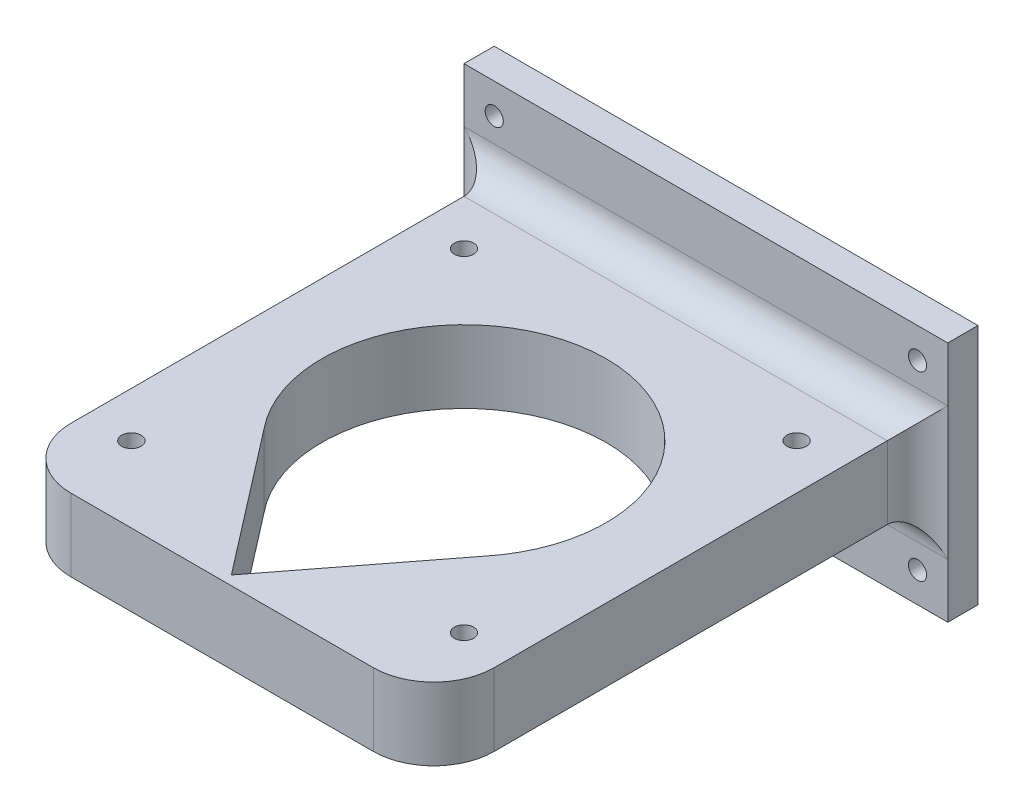
SolidWorks part; units mm, degrees
ref_plane "前视基准面" through (0, 0, 0) normal (0, 0, 1) x (1, 0, 0)
ref_plane "上视基准面" through (0, 0, 0) normal (0, 1, 0) x (1, 0, 0)
ref_plane "右视基准面" through (0, 0, 0) normal (1, 0, 0) x (0, 0, -1)
other "Configuration Table"
sketch "草图2" plane through (0, 0, 0) normal (0, 1, 0) x (1, 0, 0)
  line L1 (-35, -40) -> (35, -40)
  line L2 (-35, -40) -> (-35, 40)
  line L3 (-35, 40) -> (35, 40)
  line L4 (35, -40) -> (35, 40)
  line L5 (-35, -40) -> (35, 40) construction
  line L6 (-35, 40) -> (35, -40) construction
  line L7 (-27.5, -27.5) -> (27.5, -27.5)
  line L8 (-27.5, -27.5) -> (-27.5, 27.5)
  line L9 (-27.5, 27.5) -> (27.5, 27.5)
  line L10 (27.5, -27.5) -> (27.5, 27.5)
  line L11 (-27.5, -27.5) -> (27.5, 27.5) construction
  line L12 (-27.5, 27.5) -> (27.5, -27.5) construction
  circle A0 centre (0, 0) radius 23.5
  circle A1 centre (-27.5, 27.5) radius 1.6
  circle A2 centre (27.5, 27.5) radius 1.6
  circle A3 centre (27.5, -27.5) radius 1.6
  circle A4 centre (-27.5, -27.5) radius 1.6
  point P0 (0, 0)
  point P22 (0, 0)
  dimension "D2" = 47
  dimension "D6" = 3.2
  dimension "D1" = 70
  dimension "D3" = 80
  dimension "D4" = 55
  dimension "D5" = 55
  dimension "D7" = 4
extrude "凸台-拉伸4" add sketch "草图2" along normal blind 12 contours L1 L4 L3 L2 A4 L8 A1 L9 A2 L10 A3 L7 | A4 L7 A3 L10 A2 L9 A1 L8 A0 region at (-33.937, 0, 0) region at (-25.8186, 0, 25.8186)
sketch "草图6" plane through (0, 0, -40) normal (0, 0, -1) x (-1, 0, 0)
  line L0 (-1035, 6) -> (48965, 6) construction
  line L1 (-35, 12) -> (-35, 0) construction
  line L3 (-40, -14) -> (40, -14)
  line L4 (-40, -14) -> (-40, 26)
  line L5 (-40, 26) -> (40, 26)
  line L6 (40, -14) -> (40, 26)
  line L7 (-40, -14) -> (40, 26) construction
  line L8 (-40, 26) -> (40, -14) construction
  point P1 (0, 6)
  point P5 (-35, 6)
  dimension "D1" = 80
  dimension "D2" = 40
extrude "凸台-拉伸6" add sketch "草图6" along normal blind 5
fillet "圆角3" radius 5 1 edges at (0, 12, -40) type face fillet first side face at (-27.5, 12, -25.9) second side face at (0, 6, -40)
fillet "圆角4" radius 5 1 edges at (0, 0, -40) type face fillet first side face at (-27.5, 0, -25.9) second side face at (0, 6, -40)
fillet "圆角5" radius 5 1 edges at (35, 6, -40) type face fillet first side face at (35, 6, -12.0118) second side face at (0, 6, -40)
fillet "圆角6" radius 5 1 edges at (-35, 6, -40) type face fillet first side face at (1.25, 6, -40) second side face at (-35, 6, -12.0118)
sketch "草图7" plane through (0, 0, -40) normal (0, 0, 1) x (1, 0, 0)
  line L0 (-1040, 6) -> (48960, 6) construction
  line L1 (-40, -14) -> (-35, -14)
  line L2 (-40, -14) -> (-40, -9)
  line L3 (-40, -9) -> (-35, -9)
  line L4 (-35, -14) -> (-35, -9)
  line L5 (-40, -5) -> (-40, 17) construction
  line L6 (0, -974) -> (0, 49026) construction
  line L7 (-40, 26) -> (40, 26) construction
  circle A0 centre (-35, -9) radius 1.5
  circle A1 centre (-35, 21) radius 1.5
  circle A2 centre (35, -9) radius 1.5
  circle A3 centre (35, 21) radius 1.5
  point P11 (-40, 6)
  point P16 (0, 26)
  dimension "D3" = 3
  dimension "D1" = 5
  dimension "D2" = 5
extrude "切除-拉伸4" cut sketch "草图7" against normal blind 5 contours A1 | A3 | A2 | A0
sketch "草图8" plane through (0, 12, 0) normal (0, 1, 0) x (1, 0, 0)
  line L0 (0, 0) -> (0, -38.4612)
  line L1 (0, -38.4612) -> (-18.2335, -14.8253)
  line L2 (0, -38.4612) -> (18.2335, -14.8253)
  circle A0 centre (0, 0) radius 23.5 construction
  point P7 (18.2335, -14.8253)
  circle M11 centre (0, 0) radius 23.5
extrude "切除-拉伸6" cut sketch "草图8" against normal blind 12 contours L1 L0 M11 | L0 L2 M11 region at (5.0687, 12, 27.2438) region at (-5.0687, 12, 27.2438)
fillet "圆角7" radius 10 1 edges at (-35, 6, 40) type face fillet first side face at (0, 6, 40) second side face at (-35, 6, 2.5)
fillet "圆角8" radius 10 1 edges at (35, 6, 40) type face fillet first side face at (5, 6, 40) second side face at (35, 6, 2.5)
